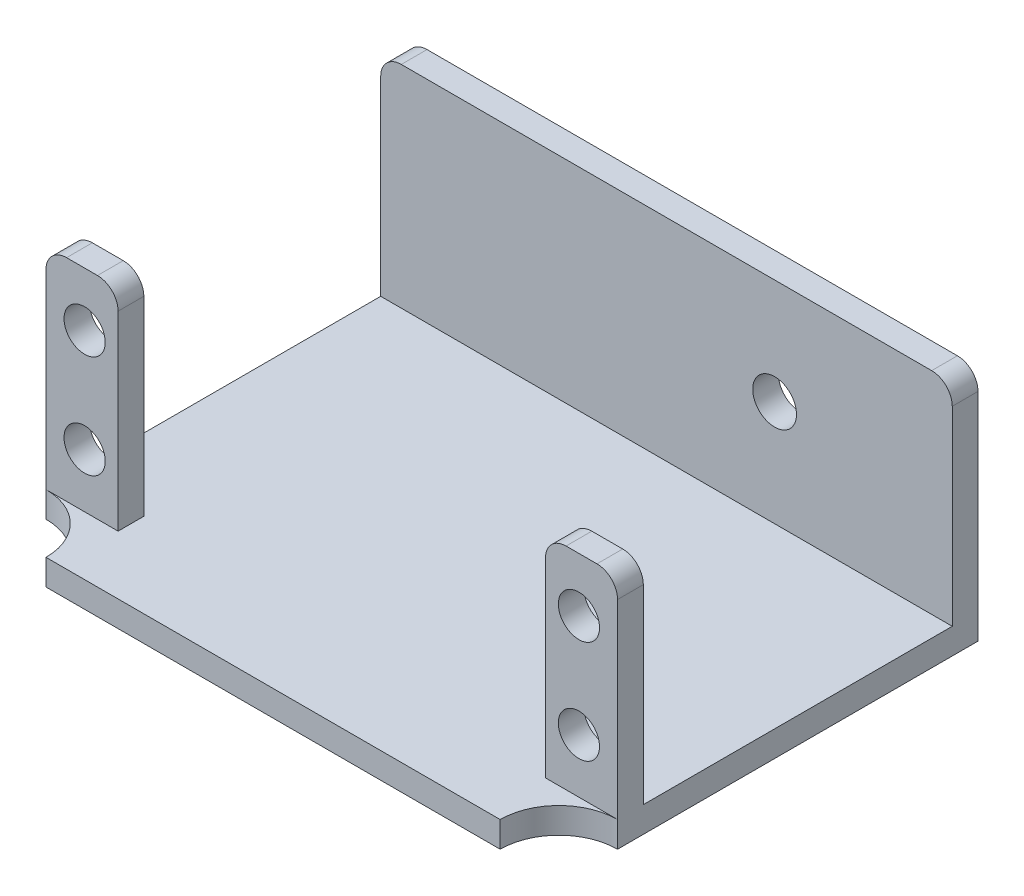
SolidWorks part; units mm, degrees
ref_plane "Front" through (0, 0, 0) normal (0, 0, 1) x (1, 0, 0)
ref_plane "Top" through (0, 0, 0) normal (0, 1, 0) x (1, 0, 0)
ref_plane "Right" through (0, 0, 0) normal (1, 0, 0) x (0, 0, -1)
sketch "Sketch1" plane through (0, 0, 0) normal (0, 1, 0) x (1, 0, 0)
  line L1 (0, 0) -> (55.5, 0)
  line L2 (0, 0) -> (0, 38.2)
  line L3 (0, 38.2) -> (55.5, 38.2)
  line L4 (55.5, 0) -> (55.5, 38.2)
  dimension "D1" = 38.2
  dimension "D2" = 55.5
extrude "bracketBase" add sketch "Sketch1" along normal blind 2.5
ref_plane "referencePlane1" through (0, 0, -8.2) normal (0, 0, 1) x (1, 0, 0)
sketch "Sketch2" plane through (0, 0, -8.2) normal (0, 0, 1) x (1, 0, 0)
  line L0 (27.75, 2.5) -> (27.75, 23) construction
  line L1 (0, 2.5) -> (7, 2.5)
  line L2 (0, 2.5) -> (0, 23)
  line L3 (0, 23) -> (7, 23)
  line L4 (7, 2.5) -> (7, 23)
  line L5 (0, 2.5) -> (55.5, 2.5) construction
  line L6 (55.5, 23) -> (48.5, 23)
  line L7 (48.5, 2.5) -> (48.5, 23)
  line L8 (55.5, 2.5) -> (48.5, 2.5)
  line L9 (55.5, 2.5) -> (55.5, 23)
  dimension "D1" = 20.5
  dimension "D2" = 7
extrude "servoMountingHoleTabs" add sketch "Sketch2" along normal blind 2.5
sketch "Sketch3" plane through (0, 0, -5.7) normal (0, 0, 1) x (1, 0, 0)
  line L0 (0, 12.75) -> (7, 12.75) construction
  line L3 (0, 23) -> (0, 2.5) construction
  line L4 (7, 2.5) -> (7, 23) construction
  line L5 (7, 23) -> (0, 23) construction
  line L6 (27.75, 2.5) -> (27.75, 23) construction
  line L7 (0, 2.5) -> (55.5, 2.5) construction
  circle A0 centre (3.75, 17.75) radius 2
  circle A1 centre (3.75, 7.75) radius 2
  circle A2 centre (51.75, 7.75) radius 2
  circle A3 centre (51.75, 17.75) radius 2
  dimension "D1" = 4
  dimension "D2" = 3.75
  dimension "D3" = 5.25
extrude "servoMountingHoles" cut sketch "Sketch3" against normal blind 2.5
sketch "Sketch4" plane through (0, 0, 0) normal (0, 1, 0) x (1, 0, 0)
  line L0 (55.5, 8.2) -> (55.5, 38.2) construction
  line L1 (0, 38.2) -> (55.5, 38.2)
  line L2 (0, 38.2) -> (0, 40.7)
  line L3 (0, 40.7) -> (55.5, 40.7)
  line L4 (55.5, 38.2) -> (55.5, 40.7)
  dimension "D1" = 2.5
extrude "baseWall" add sketch "Sketch4" along normal up to surface (23 mm away) up to face at (3.5, 23, -6.95)
sketch "Sketch5" plane through (0, 0, -38.2) normal (0, 0, 1) x (1, 0, 0)
  line L0 (0, 12.75) -> (55.5, 12.75) construction
  line L1 (0, 23) -> (0, 2.5) construction
  line L2 (55.5, 2.5) -> (55.5, 23) construction
  circle A0 centre (38.25, 12.75) radius 2.125
  dimension "D1" = 4.25
  dimension "D2" = 17.25
extrude "M4mountingHole" cut sketch "Sketch5" against normal blind 2.5
sketch "Sketch6" plane through (0, 2.5, 0) normal (0, 1, 0) x (1, 0, 0)
  circle A0 centre (0, 0) radius 5.7
  circle A1 centre (55.5, 0) radius 5.7
extrude "baseTrim" cut sketch "Sketch6" against normal blind 2.5
fillet "Fillet1" radius 2 6 edges at (7, 23, -6.95) (48.5, 23, -6.95) (0, 23, -6.95) (55.5, 23, -6.95) (55.5, 23, -39.45) (0, 23, -39.45)
